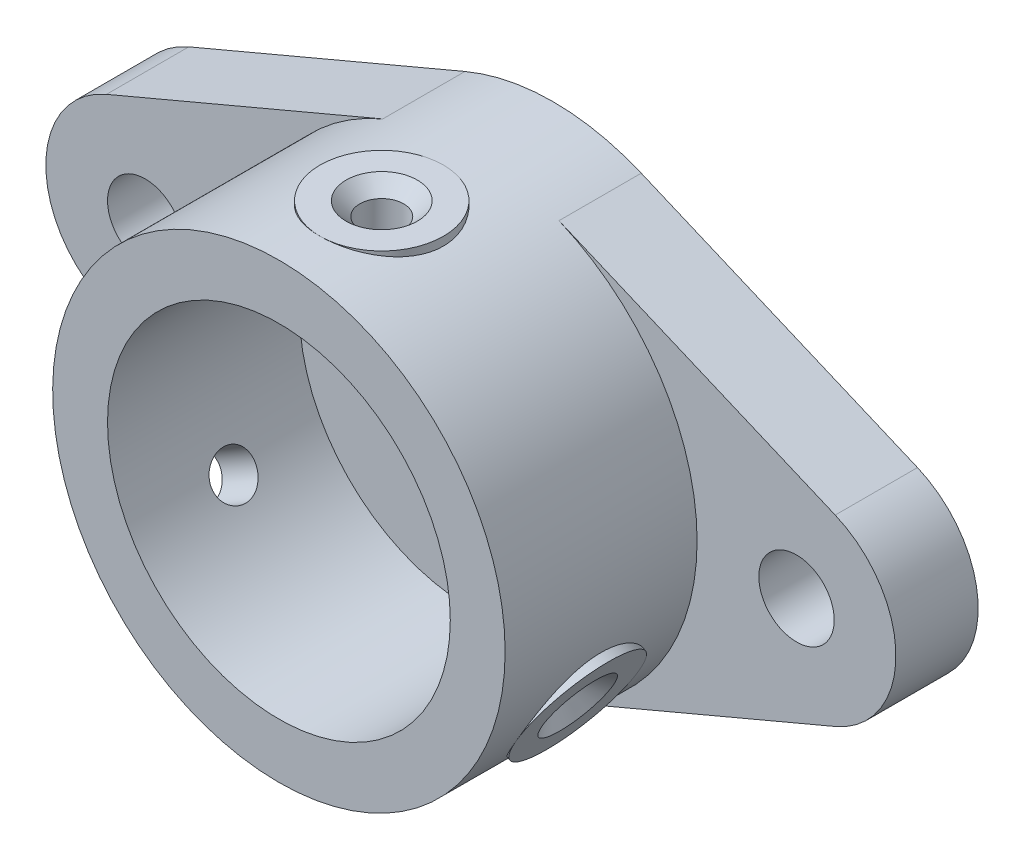
SolidWorks part; units mm, degrees
ref_plane "Front Plane" through (0, 0, 0) normal (0, 0, 1) x (1, 0, 0)
ref_plane "Top Plane" through (0, 0, 0) normal (0, 1, 0) x (1, 0, 0)
ref_plane "Right Plane" through (0, 0, 0) normal (1, 0, 0) x (0, 0, -1)
sketch "Sketch1" plane through (0, 0, 0) normal (0, 0, 1) x (1, 0, 0)
  circle A0 centre (0, 0) radius 12.5
  circle A1 centre (0, 0) radius 16.5
  dimension "D1" = 25
  dimension "D2" = 4
extrude "Boss-Extrude1" add sketch "Sketch1" along normal blind 15
sketch "Sketch2" plane through (0, 0, 0) normal (0, 0, -1) x (-1, 0, 0)
  circle A0 centre (0, 0) radius 16.5
  circle A1 centre (0, 0) radius 16.5 construction
extrude "Boss-Extrude2" add sketch "Sketch2" along normal blind 5
ref_plane "Plane1" through (0, 16.5, 0) normal (0, 1, 0) x (1, 0, 0)
sketch "Sketch3" plane through (0, 16.5, 0) normal (0, 1, 0) x (1, 0, 0)
  line L0 (-16.5, -15) -> (16.5, -15) construction
  circle A0 centre (0, -7.5) radius 4.5
  dimension "D1" = 9
  dimension "D2" = 7.5
extrude "Boss-Extrude3" add sketch "Sketch3" against normal up to surface up to face at (16.5, 0, 15)
sketch "Sketch4" plane through (0, 16.5, 0) normal (0, 1, 0) x (1, 0, 0)
  line L0 (-16.5, -15) -> (16.5, -15) construction
  circle A0 centre (0, -7.5) radius 1.6
  dimension "D1" = 3.2
  dimension "D2" = 7.5
extrude "Cut-Extrude1" cut sketch "Sketch4" against normal up to surface (4 mm away) up to face at (12.5, 0, 15)
pattern_circular "CirPattern1" count 3 over 360 about axis through (0, 0, 15) along (0, 0, 1) of "Cut-Extrude1", "Boss-Extrude3"
chamfer "Chamfer1" distance 1 angle 45 3 edges at (-14.2894, -8.25, 9.1) (14.2894, -8.25, 9.1) (0, 16.5, 9.1)
sketch "Sketch5" plane through (0, 0, -5) normal (0, 0, -1) x (-1, 0, 0)
  line L0 (26.5737, 6.6775) -> (6.4263, 15.1971)
  line L1 (26.5737, -6.6775) -> (6.4263, -15.1971)
  line L2 (-6.4263, 15.1971) -> (-26.5737, 6.6775)
  line L3 (-6.4263, -15.1971) -> (-26.5737, -6.6775)
  circle A0 centre (23.75, 0) radius 2.75
  circle A1 centre (-23.75, 0) radius 2.75
  arc A2 (26.5737, -6.6775) -> (26.5737, 6.6775) centre (23.75, 0) ccw
  arc A3 (-26.5737, 6.6775) -> (-26.5737, -6.6775) centre (-23.75, 0) ccw
  circle A4 centre (0, 0) radius 16.5 construction
  circle A6 centre (0, 0) radius 16.5 construction
  circle A8 centre (0, 0) radius 16.5 construction
  arc A9 (6.4263, 15.1971) -> (-6.4263, 15.1971) centre (0, 0) ccw
  arc A10 (6.4263, -15.1971) -> (-6.4263, -15.1971) centre (0, 0) cw
  dimension "D3" = 5.5
  dimension "D1" = 23.75
  dimension "D2" = 23.75
extrude "Boss-Extrude4" add sketch "Sketch5" against normal blind 6
sketch "Sketch6" plane through (0, 0, 1) normal (0, 0, 1) x (1, 0, 0)
  circle A0 centre (-23.75, 0) radius 4.5
  circle A1 centre (23.75, 0) radius 4.5
  dimension "D1" = 9
extrude "Cut-Extrude2" [suppressed] cut sketch "Sketch6" against normal blind 5
